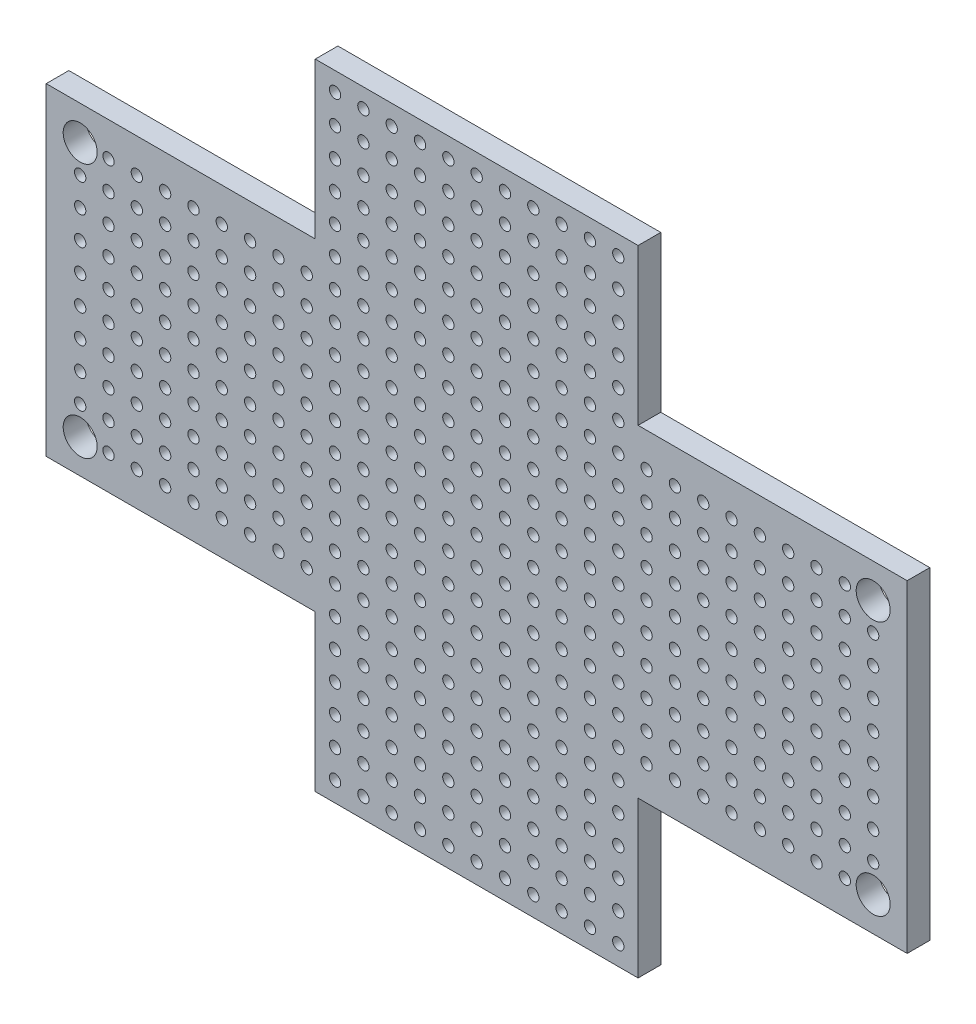
SolidWorks part; units mm, degrees
ref_plane "Front Plane" through (0, 0, 0) normal (0, 0, 1) x (1, 0, 0)
ref_plane "Top Plane" through (0, 0, 0) normal (0, 1, 0) x (1, 0, 0)
ref_plane "Right Plane" through (0, 0, 0) normal (1, 0, 0) x (0, 0, -1)
sketch "Sketch1" plane through (0, 0, 0) normal (0, 0, 1) x (1, 0, 0)
  line L0 (0, 14.25) -> (76, 14.25) construction
  line L1 (0, 0) -> (23.75, 0)
  line L2 (0, 0) -> (0, 28.5)
  line L3 (0, 28.5) -> (23.75, 28.5)
  line L4 (76, 0) -> (76, 28.5)
  line L5 (38, -42.734) -> (38, 127.234) construction
  line L6 (0, 25.5) -> (76, 25.5) construction
  line L7 (76, 3) -> (0, 3) construction
  line L8 (73, 0) -> (73, 28.5) construction
  line L9 (3, 0) -> (3, 28.5) construction
  line L10 (28, 35.5) -> (28, 38.04) construction
  line L12 (23.75, 28.5) -> (23.75, 42.25)
  line L13 (23.75, 42.25) -> (52.25, 42.25)
  line L14 (52.25, 42.25) -> (52.25, 28.5)
  line L15 (52.25, -13.75) -> (52.25, 0)
  line L16 (23.75, -13.75) -> (52.25, -13.75)
  line L17 (23.75, 0) -> (23.75, -13.75)
  line L18 (52.25, 28.5) -> (76, 28.5)
  line L19 (52.25, 0) -> (76, 0)
  line L20 (25.5, 25.5) -> (25.5, 28) construction
  circle A0 centre (3, 25.5) radius 1.5
  circle A1 centre (73, 25.5) radius 1.5
  circle A2 centre (3, 3) radius 1.5
  circle A3 centre (73, 3) radius 1.5
  circle A4 centre (28, 38.04) radius 0.5
  circle A5 centre (5.5, 3) radius 0.5
  circle A6 centre (8, 3) radius 0.5
  circle A7 centre (10.5, 3) radius 0.5
  circle A8 centre (13, 3) radius 0.5
  circle A9 centre (15.5, 3) radius 0.5
  circle A10 centre (18, 3) radius 0.5
  circle A11 centre (20.5, 3) radius 0.5
  circle A12 centre (23, 3) radius 0.5
  circle A13 centre (25.5, 3) radius 0.5
  circle A14 centre (28, 3) radius 0.5
  circle A15 centre (30.5, 3) radius 0.5
  circle A16 centre (33, 3) radius 0.5
  circle A17 centre (35.5, 3) radius 0.5
  circle A18 centre (38, 3) radius 0.5
  circle A19 centre (40.5, 3) radius 0.5
  circle A20 centre (43, 3) radius 0.5
  circle A21 centre (45.5, 3) radius 0.5
  circle A22 centre (48, 3) radius 0.5
  circle A23 centre (50.5, 3) radius 0.5
  circle A24 centre (53, 3) radius 0.5
  circle A25 centre (55.5, 3) radius 0.5
  circle A26 centre (58, 3) radius 0.5
  circle A27 centre (60.5, 3) radius 0.5
  circle A28 centre (63, 3) radius 0.5
  circle A29 centre (65.5, 3) radius 0.5
  circle A30 centre (68, 3) radius 0.5
  circle A31 centre (70.5, 3) radius 0.5
  circle A32 centre (25.5, 38.04) radius 0.5
  circle A33 centre (5.5, 5.5) radius 0.5
  circle A34 centre (8, 5.5) radius 0.5
  circle A35 centre (10.5, 5.5) radius 0.5
  circle A36 centre (13, 5.5) radius 0.5
  circle A37 centre (15.5, 5.5) radius 0.5
  circle A38 centre (18, 5.5) radius 0.5
  circle A39 centre (20.5, 5.5) radius 0.5
  circle A40 centre (23, 5.5) radius 0.5
  circle A41 centre (25.5, 5.5) radius 0.5
  circle A42 centre (28, 5.5) radius 0.5
  circle A43 centre (30.5, 5.5) radius 0.5
  circle A44 centre (33, 5.5) radius 0.5
  circle A45 centre (35.5, 5.5) radius 0.5
  circle A46 centre (38, 5.5) radius 0.5
  circle A47 centre (40.5, 5.5) radius 0.5
  circle A48 centre (43, 5.5) radius 0.5
  circle A49 centre (45.5, 5.5) radius 0.5
  circle A50 centre (48, 5.5) radius 0.5
  circle A51 centre (50.5, 5.5) radius 0.5
  circle A52 centre (53, 5.5) radius 0.5
  circle A53 centre (55.5, 5.5) radius 0.5
  circle A54 centre (58, 5.5) radius 0.5
  circle A55 centre (60.5, 5.5) radius 0.5
  circle A56 centre (63, 5.5) radius 0.5
  circle A57 centre (65.5, 5.5) radius 0.5
  circle A58 centre (68, 5.5) radius 0.5
  circle A59 centre (70.5, 5.5) radius 0.5
  circle A60 centre (73, 5.5) radius 0.5
  circle A61 centre (5.5, 8) radius 0.5
  circle A62 centre (8, 8) radius 0.5
  circle A63 centre (10.5, 8) radius 0.5
  circle A64 centre (13, 8) radius 0.5
  circle A65 centre (15.5, 8) radius 0.5
  circle A66 centre (18, 8) radius 0.5
  circle A67 centre (20.5, 8) radius 0.5
  circle A68 centre (23, 8) radius 0.5
  circle A69 centre (25.5, 8) radius 0.5
  circle A70 centre (28, 8) radius 0.5
  circle A71 centre (30.5, 8) radius 0.5
  circle A72 centre (33, 8) radius 0.5
  circle A73 centre (35.5, 8) radius 0.5
  circle A74 centre (38, 8) radius 0.5
  circle A75 centre (40.5, 8) radius 0.5
  circle A76 centre (43, 8) radius 0.5
  circle A77 centre (45.5, 8) radius 0.5
  circle A78 centre (48, 8) radius 0.5
  circle A79 centre (50.5, 8) radius 0.5
  circle A80 centre (53, 8) radius 0.5
  circle A81 centre (55.5, 8) radius 0.5
  circle A82 centre (58, 8) radius 0.5
  circle A83 centre (60.5, 8) radius 0.5
  circle A84 centre (63, 8) radius 0.5
  circle A85 centre (65.5, 8) radius 0.5
  circle A86 centre (68, 8) radius 0.5
  circle A87 centre (70.5, 8) radius 0.5
  circle A88 centre (73, 8) radius 0.5
  circle A89 centre (5.5, 10.5) radius 0.5
  circle A90 centre (8, 10.5) radius 0.5
  circle A91 centre (10.5, 10.5) radius 0.5
  circle A92 centre (13, 10.5) radius 0.5
  circle A93 centre (15.5, 10.5) radius 0.5
  circle A94 centre (18, 10.5) radius 0.5
  circle A95 centre (20.5, 10.5) radius 0.5
  circle A96 centre (23, 10.5) radius 0.5
  circle A97 centre (25.5, 10.5) radius 0.5
  circle A98 centre (28, 10.5) radius 0.5
  circle A99 centre (30.5, 10.5) radius 0.5
  circle A100 centre (33, 10.5) radius 0.5
  circle A101 centre (35.5, 10.5) radius 0.5
  circle A102 centre (38, 10.5) radius 0.5
  circle A103 centre (40.5, 10.5) radius 0.5
  circle A104 centre (43, 10.5) radius 0.5
  circle A105 centre (45.5, 10.5) radius 0.5
  circle A106 centre (48, 10.5) radius 0.5
  circle A107 centre (50.5, 10.5) radius 0.5
  circle A108 centre (53, 10.5) radius 0.5
  circle A109 centre (55.5, 10.5) radius 0.5
  circle A110 centre (58, 10.5) radius 0.5
  circle A111 centre (60.5, 10.5) radius 0.5
  circle A112 centre (63, 10.5) radius 0.5
  circle A113 centre (65.5, 10.5) radius 0.5
  circle A114 centre (68, 10.5) radius 0.5
  circle A115 centre (70.5, 10.5) radius 0.5
  circle A116 centre (73, 10.5) radius 0.5
  circle A117 centre (5.5, 13) radius 0.5
  circle A118 centre (8, 13) radius 0.5
  circle A119 centre (10.5, 13) radius 0.5
  circle A120 centre (13, 13) radius 0.5
  circle A121 centre (15.5, 13) radius 0.5
  circle A122 centre (18, 13) radius 0.5
  circle A123 centre (20.5, 13) radius 0.5
  circle A124 centre (23, 13) radius 0.5
  circle A125 centre (25.5, 13) radius 0.5
  circle A126 centre (28, 13) radius 0.5
  circle A127 centre (30.5, 13) radius 0.5
  circle A128 centre (33, 13) radius 0.5
  circle A129 centre (35.5, 13) radius 0.5
  circle A130 centre (38, 13) radius 0.5
  circle A131 centre (40.5, 13) radius 0.5
  circle A132 centre (43, 13) radius 0.5
  circle A133 centre (45.5, 13) radius 0.5
  circle A134 centre (48, 13) radius 0.5
  circle A135 centre (50.5, 13) radius 0.5
  circle A136 centre (53, 13) radius 0.5
  circle A137 centre (55.5, 13) radius 0.5
  circle A138 centre (58, 13) radius 0.5
  circle A139 centre (60.5, 13) radius 0.5
  circle A140 centre (63, 13) radius 0.5
  circle A141 centre (65.5, 13) radius 0.5
  circle A142 centre (68, 13) radius 0.5
  circle A143 centre (70.5, 13) radius 0.5
  circle A144 centre (73, 13) radius 0.5
  circle A145 centre (5.5, 15.5) radius 0.5
  circle A146 centre (8, 15.5) radius 0.5
  circle A147 centre (10.5, 15.5) radius 0.5
  circle A148 centre (13, 15.5) radius 0.5
  circle A149 centre (15.5, 15.5) radius 0.5
  circle A150 centre (18, 15.5) radius 0.5
  circle A151 centre (20.5, 15.5) radius 0.5
  circle A152 centre (23, 15.5) radius 0.5
  circle A153 centre (25.5, 15.5) radius 0.5
  circle A154 centre (28, 15.5) radius 0.5
  circle A155 centre (30.5, 15.5) radius 0.5
  circle A156 centre (33, 15.5) radius 0.5
  circle A157 centre (35.5, 15.5) radius 0.5
  circle A158 centre (38, 15.5) radius 0.5
  circle A159 centre (40.5, 15.5) radius 0.5
  circle A160 centre (43, 15.5) radius 0.5
  circle A161 centre (45.5, 15.5) radius 0.5
  circle A162 centre (48, 15.5) radius 0.5
  circle A163 centre (50.5, 15.5) radius 0.5
  circle A164 centre (53, 15.5) radius 0.5
  circle A165 centre (55.5, 15.5) radius 0.5
  circle A166 centre (58, 15.5) radius 0.5
  circle A167 centre (60.5, 15.5) radius 0.5
  circle A168 centre (63, 15.5) radius 0.5
  circle A169 centre (65.5, 15.5) radius 0.5
  circle A170 centre (68, 15.5) radius 0.5
  circle A171 centre (70.5, 15.5) radius 0.5
  circle A172 centre (73, 15.5) radius 0.5
  circle A173 centre (5.5, 18) radius 0.5
  circle A174 centre (8, 18) radius 0.5
  circle A175 centre (10.5, 18) radius 0.5
  circle A176 centre (13, 18) radius 0.5
  circle A177 centre (15.5, 18) radius 0.5
  circle A178 centre (18, 18) radius 0.5
  circle A179 centre (20.5, 18) radius 0.5
  circle A180 centre (23, 18) radius 0.5
  circle A181 centre (25.5, 18) radius 0.5
  circle A182 centre (28, 18) radius 0.5
  circle A183 centre (30.5, 18) radius 0.5
  circle A184 centre (33, 18) radius 0.5
  circle A185 centre (35.5, 18) radius 0.5
  circle A186 centre (38, 18) radius 0.5
  circle A187 centre (40.5, 18) radius 0.5
  circle A188 centre (43, 18) radius 0.5
  circle A189 centre (45.5, 18) radius 0.5
  circle A190 centre (48, 18) radius 0.5
  circle A191 centre (50.5, 18) radius 0.5
  circle A192 centre (53, 18) radius 0.5
  circle A193 centre (55.5, 18) radius 0.5
  circle A194 centre (58, 18) radius 0.5
  circle A195 centre (60.5, 18) radius 0.5
  circle A196 centre (63, 18) radius 0.5
  circle A197 centre (65.5, 18) radius 0.5
  circle A198 centre (68, 18) radius 0.5
  circle A199 centre (70.5, 18) radius 0.5
  circle A200 centre (73, 18) radius 0.5
  circle A201 centre (5.5, 20.5) radius 0.5
  circle A202 centre (8, 20.5) radius 0.5
  circle A203 centre (10.5, 20.5) radius 0.5
  circle A204 centre (13, 20.5) radius 0.5
  circle A205 centre (15.5, 20.5) radius 0.5
  circle A206 centre (18, 20.5) radius 0.5
  circle A207 centre (20.5, 20.5) radius 0.5
  circle A208 centre (23, 20.5) radius 0.5
  circle A209 centre (25.5, 20.5) radius 0.5
  circle A210 centre (28, 20.5) radius 0.5
  circle A211 centre (30.5, 20.5) radius 0.5
  circle A212 centre (33, 20.5) radius 0.5
  circle A213 centre (35.5, 20.5) radius 0.5
  circle A214 centre (38, 20.5) radius 0.5
  circle A215 centre (40.5, 20.5) radius 0.5
  circle A216 centre (43, 20.5) radius 0.5
  circle A217 centre (45.5, 20.5) radius 0.5
  circle A218 centre (48, 20.5) radius 0.5
  circle A219 centre (50.5, 20.5) radius 0.5
  circle A220 centre (53, 20.5) radius 0.5
  circle A221 centre (55.5, 20.5) radius 0.5
  circle A222 centre (58, 20.5) radius 0.5
  circle A223 centre (60.5, 20.5) radius 0.5
  circle A224 centre (63, 20.5) radius 0.5
  circle A225 centre (65.5, 20.5) radius 0.5
  circle A226 centre (68, 20.5) radius 0.5
  circle A227 centre (70.5, 20.5) radius 0.5
  circle A228 centre (73, 20.5) radius 0.5
  circle A229 centre (5.5, 23) radius 0.5
  circle A230 centre (8, 23) radius 0.5
  circle A231 centre (10.5, 23) radius 0.5
  circle A232 centre (13, 23) radius 0.5
  circle A233 centre (15.5, 23) radius 0.5
  circle A234 centre (18, 23) radius 0.5
  circle A235 centre (20.5, 23) radius 0.5
  circle A236 centre (23, 23) radius 0.5
  circle A237 centre (25.5, 23) radius 0.5
  circle A238 centre (28, 23) radius 0.5
  circle A239 centre (30.5, 23) radius 0.5
  circle A240 centre (33, 23) radius 0.5
  circle A241 centre (35.5, 23) radius 0.5
  circle A242 centre (38, 23) radius 0.5
  circle A243 centre (40.5, 23) radius 0.5
  circle A244 centre (43, 23) radius 0.5
  circle A245 centre (45.5, 23) radius 0.5
  circle A246 centre (48, 23) radius 0.5
  circle A247 centre (50.5, 23) radius 0.5
  circle A248 centre (53, 23) radius 0.5
  circle A249 centre (55.5, 23) radius 0.5
  circle A250 centre (58, 23) radius 0.5
  circle A251 centre (60.5, 23) radius 0.5
  circle A252 centre (63, 23) radius 0.5
  circle A253 centre (65.5, 23) radius 0.5
  circle A254 centre (68, 23) radius 0.5
  circle A255 centre (70.5, 23) radius 0.5
  circle A256 centre (73, 23) radius 0.5
  circle A257 centre (5.5, 25.5) radius 0.5
  circle A258 centre (8, 25.5) radius 0.5
  circle A259 centre (10.5, 25.5) radius 0.5
  circle A260 centre (13, 25.5) radius 0.5
  circle A261 centre (15.5, 25.5) radius 0.5
  circle A262 centre (18, 25.5) radius 0.5
  circle A263 centre (20.5, 25.5) radius 0.5
  circle A264 centre (23, 25.5) radius 0.5
  circle A265 centre (25.5, 25.5) radius 0.5
  circle A266 centre (28, 25.5) radius 0.5
  circle A267 centre (30.5, 25.5) radius 0.5
  circle A268 centre (33, 25.5) radius 0.5
  circle A269 centre (35.5, 25.5) radius 0.5
  circle A270 centre (38, 25.5) radius 0.5
  circle A271 centre (40.5, 25.5) radius 0.5
  circle A272 centre (43, 25.5) radius 0.5
  circle A273 centre (45.5, 25.5) radius 0.5
  circle A274 centre (48, 25.5) radius 0.5
  circle A275 centre (50.5, 25.5) radius 0.5
  circle A276 centre (53, 25.5) radius 0.5
  circle A277 centre (55.5, 25.5) radius 0.5
  circle A278 centre (58, 25.5) radius 0.5
  circle A279 centre (60.5, 25.5) radius 0.5
  circle A280 centre (63, 25.5) radius 0.5
  circle A281 centre (65.5, 25.5) radius 0.5
  circle A282 centre (68, 25.5) radius 0.5
  circle A283 centre (70.5, 25.5) radius 0.5
  circle A284 centre (28, 40.58) radius 0.5
  circle A285 centre (3, 5.5) radius 0.5
  circle A286 centre (3, 8) radius 0.5
  circle A287 centre (3, 10.5) radius 0.5
  circle A288 centre (3, 13) radius 0.5
  circle A289 centre (3, 15.5) radius 0.5
  circle A290 centre (3, 18) radius 0.5
  circle A291 centre (3, 20.5) radius 0.5
  circle A292 centre (3, 23) radius 0.5
  circle A293 centre (25.5, 40.58) radius 0.5
  circle A294 centre (25.5, 28) radius 0.5
  circle A295 centre (28, 28) radius 0.5
  circle A296 centre (30.5, 28) radius 0.5
  circle A297 centre (33, 28) radius 0.5
  circle A298 centre (35.5, 28) radius 0.5
  circle A299 centre (38, 28) radius 0.5
  circle A300 centre (40.5, 28) radius 0.5
  circle A301 centre (43, 28) radius 0.5
  circle A302 centre (45.5, 28) radius 0.5
  circle A303 centre (48, 28) radius 0.5
  circle A304 centre (50.5, 28) radius 0.5
  circle A305 centre (25.5, 30.5) radius 0.5
  circle A306 centre (28, 30.5) radius 0.5
  circle A307 centre (30.5, 30.5) radius 0.5
  circle A308 centre (33, 30.5) radius 0.5
  circle A309 centre (35.5, 30.5) radius 0.5
  circle A310 centre (38, 30.5) radius 0.5
  circle A311 centre (40.5, 30.5) radius 0.5
  circle A312 centre (43, 30.5) radius 0.5
  circle A313 centre (45.5, 30.5) radius 0.5
  circle A314 centre (48, 30.5) radius 0.5
  circle A315 centre (50.5, 30.5) radius 0.5
  circle A316 centre (25.5, 33) radius 0.5
  circle A317 centre (28, 33) radius 0.5
  circle A318 centre (30.5, 33) radius 0.5
  circle A319 centre (33, 33) radius 0.5
  circle A320 centre (35.5, 33) radius 0.5
  circle A321 centre (38, 33) radius 0.5
  circle A322 centre (40.5, 33) radius 0.5
  circle A323 centre (43, 33) radius 0.5
  circle A324 centre (45.5, 33) radius 0.5
  circle A325 centre (48, 33) radius 0.5
  circle A326 centre (50.5, 33) radius 0.5
  circle A327 centre (25.5, 35.5) radius 0.5
  circle A328 centre (28, 35.5) radius 0.5
  circle A329 centre (30.5, 35.5) radius 0.5
  circle A330 centre (33, 35.5) radius 0.5
  circle A331 centre (35.5, 35.5) radius 0.5
  circle A332 centre (38, 35.5) radius 0.5
  circle A333 centre (40.5, 35.5) radius 0.5
  circle A334 centre (43, 35.5) radius 0.5
  circle A335 centre (45.5, 35.5) radius 0.5
  circle A336 centre (48, 35.5) radius 0.5
  circle A337 centre (50.5, 35.5) radius 0.5
  circle A338 centre (50.5, 38.04) radius 0.5
  circle A339 centre (48, 38.04) radius 0.5
  circle A340 centre (30.5, 38) radius 0.5
  circle A341 centre (33, 38) radius 0.5
  circle A342 centre (35.5, 38) radius 0.5
  circle A343 centre (38, 38) radius 0.5
  circle A344 centre (40.5, 38) radius 0.5
  circle A345 centre (43, 38) radius 0.5
  circle A346 centre (45.5, 38) radius 0.5
  circle A347 centre (50.5, 40.58) radius 0.5
  circle A348 centre (48, 40.58) radius 0.5
  circle A351 centre (30.5, 40.5) radius 0.5
  circle A352 centre (33, 40.5) radius 0.5
  circle A353 centre (35.5, 40.5) radius 0.5
  circle A354 centre (38, 40.5) radius 0.5
  circle A355 centre (40.5, 40.5) radius 0.5
  circle A356 centre (43, 40.5) radius 0.5
  circle A357 centre (45.5, 40.5) radius 0.5
  circle A384 centre (25.5, -12) radius 0.5
  circle A385 centre (25.5, -9.5) radius 0.5
  circle A386 centre (25.5, -7) radius 0.5
  circle A387 centre (25.5, -4.5) radius 0.5
  circle A388 centre (25.5, -2) radius 0.5
  circle A389 centre (25.5, 0.5) radius 0.5
  circle A410 centre (50.5, -12) radius 0.5
  circle A411 centre (48, -12) radius 0.5
  circle A412 centre (45.5, -12) radius 0.5
  circle A413 centre (43, -12) radius 0.5
  circle A414 centre (40.5, -12) radius 0.5
  circle A415 centre (38, -12) radius 0.5
  circle A416 centre (35.5, -12) radius 0.5
  circle A417 centre (33, -12) radius 0.5
  circle A418 centre (30.5, -12) radius 0.5
  circle A419 centre (28, -12) radius 0.5
  circle A420 centre (50.5, -9.5) radius 0.5
  circle A421 centre (48, -9.5) radius 0.5
  circle A422 centre (45.5, -9.5) radius 0.5
  circle A423 centre (43, -9.5) radius 0.5
  circle A424 centre (40.5, -9.5) radius 0.5
  circle A425 centre (38, -9.5) radius 0.5
  circle A426 centre (35.5, -9.5) radius 0.5
  circle A427 centre (33, -9.5) radius 0.5
  circle A428 centre (30.5, -9.5) radius 0.5
  circle A429 centre (28, -9.5) radius 0.5
  circle A430 centre (50.5, -7) radius 0.5
  circle A431 centre (48, -7) radius 0.5
  circle A432 centre (45.5, -7) radius 0.5
  circle A433 centre (43, -7) radius 0.5
  circle A434 centre (40.5, -7) radius 0.5
  circle A435 centre (38, -7) radius 0.5
  circle A436 centre (35.5, -7) radius 0.5
  circle A437 centre (33, -7) radius 0.5
  circle A438 centre (30.5, -7) radius 0.5
  circle A439 centre (28, -7) radius 0.5
  circle A440 centre (50.5, -4.5) radius 0.5
  circle A441 centre (48, -4.5) radius 0.5
  circle A442 centre (45.5, -4.5) radius 0.5
  circle A443 centre (43, -4.5) radius 0.5
  circle A444 centre (40.5, -4.5) radius 0.5
  circle A445 centre (38, -4.5) radius 0.5
  circle A446 centre (35.5, -4.5) radius 0.5
  circle A447 centre (33, -4.5) radius 0.5
  circle A448 centre (30.5, -4.5) radius 0.5
  circle A449 centre (28, -4.5) radius 0.5
  circle A450 centre (50.5, -2) radius 0.5
  circle A451 centre (48, -2) radius 0.5
  circle A452 centre (45.5, -2) radius 0.5
  circle A453 centre (43, -2) radius 0.5
  circle A454 centre (40.5, -2) radius 0.5
  circle A455 centre (38, -2) radius 0.5
  circle A456 centre (35.5, -2) radius 0.5
  circle A457 centre (33, -2) radius 0.5
  circle A458 centre (30.5, -2) radius 0.5
  circle A459 centre (28, -2) radius 0.5
  circle A460 centre (50.5, 0.5) radius 0.5
  circle A461 centre (48, 0.5) radius 0.5
  circle A462 centre (45.5, 0.5) radius 0.5
  circle A463 centre (43, 0.5) radius 0.5
  circle A464 centre (40.5, 0.5) radius 0.5
  circle A465 centre (38, 0.5) radius 0.5
  circle A466 centre (35.5, 0.5) radius 0.5
  circle A467 centre (33, 0.5) radius 0.5
  circle A468 centre (30.5, 0.5) radius 0.5
  circle A469 centre (28, 0.5) radius 0.5
  circle A571 centre (3, 3) radius 1.5 [skipped]
  circle A572 centre (25.5, 40.5) radius 0.5 [skipped]
  circle A573 centre (50.5, 40.5) radius 0.5 [skipped]
  circle A574 centre (25.5, 38) radius 0.5 [skipped]
  circle A575 centre (28, 38) radius 0.5 [skipped]
  circle A576 centre (28, 40.5) radius 0.5 [skipped]
  circle A577 centre (48, 40.5) radius 0.5 [skipped]
  circle A578 centre (48, 38) radius 0.5 [skipped]
  circle A579 centre (50.5, 38) radius 0.5 [skipped]
  point P611 (38, 42.25)
  point P612 (38, 14.25)
  dimension "D3" = 3
  dimension "D8" = 3
  dimension "D9" = 11.25
  dimension "D10" = 76
  dimension "D11" = 35
  dimension "D12" = 3
  dimension "D13" = 2.54
  dimension "D14" = 3
  dimension "D15" = 1
  dimension "D20" = 2.5
  dimension "D1" = 28.5
  dimension "D2" = 3
  dimension "D4" = 3
  dimension "D5" = 3
  dimension "D16" = 28.5
  dimension "D17" = 13.75
  dimension "D19" = 2.5
  dimension "D6" = 2
  dimension "D7" = 2
  dimension "D18" = 7
extrude "Boss-Extrude1" add sketch "Sketch1" along normal blind 2
fillet "Fillet1" [suppressed] radius 1.27
ref_plane "Plane1" [suppressed] through (0, 14.25, 0) normal (0, -1, 0) x (1, 0, 0)
ref_plane "Plane2" [suppressed] through (38, 0, 0) normal (1, 0, 0) x (0, 0, -1)
